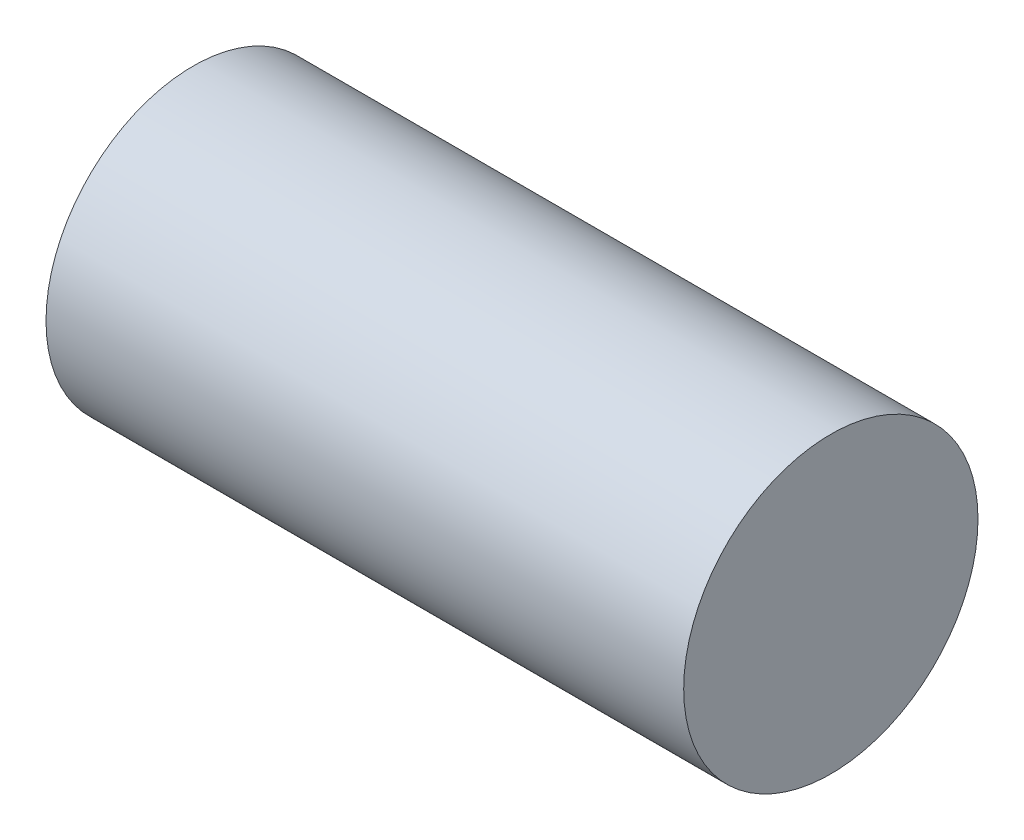
SolidWorks part; units mm, degrees
material "Chrome Stainless Steel"
ref_plane "Front Plane" through (0, 0, 0) normal (0, 0, 1) x (1, 0, 0)
ref_plane "Top Plane" through (0, 0, 0) normal (0, 1, 0) x (1, 0, 0)
ref_plane "Right Plane" through (0, 0, 0) normal (1, 0, 0) x (0, 0, -1)
other "Configuration Table"
sketch "Sketch1" plane through (0, 0, 0) normal (1, 0, 0) x (0, 0, -1)
  circle A0 centre (0, 0) radius 6
  dimension "D1" = 12
extrude "Boss-Extrude1" add sketch "Sketch1" along normal blind 26
ref_plane "Plane1" through (13, 0, 0) normal (1, 0, 0) x (0, 0, -1)
ref_axis "Axis1" through (26, 0, 0) along (-1, 0, 0)
